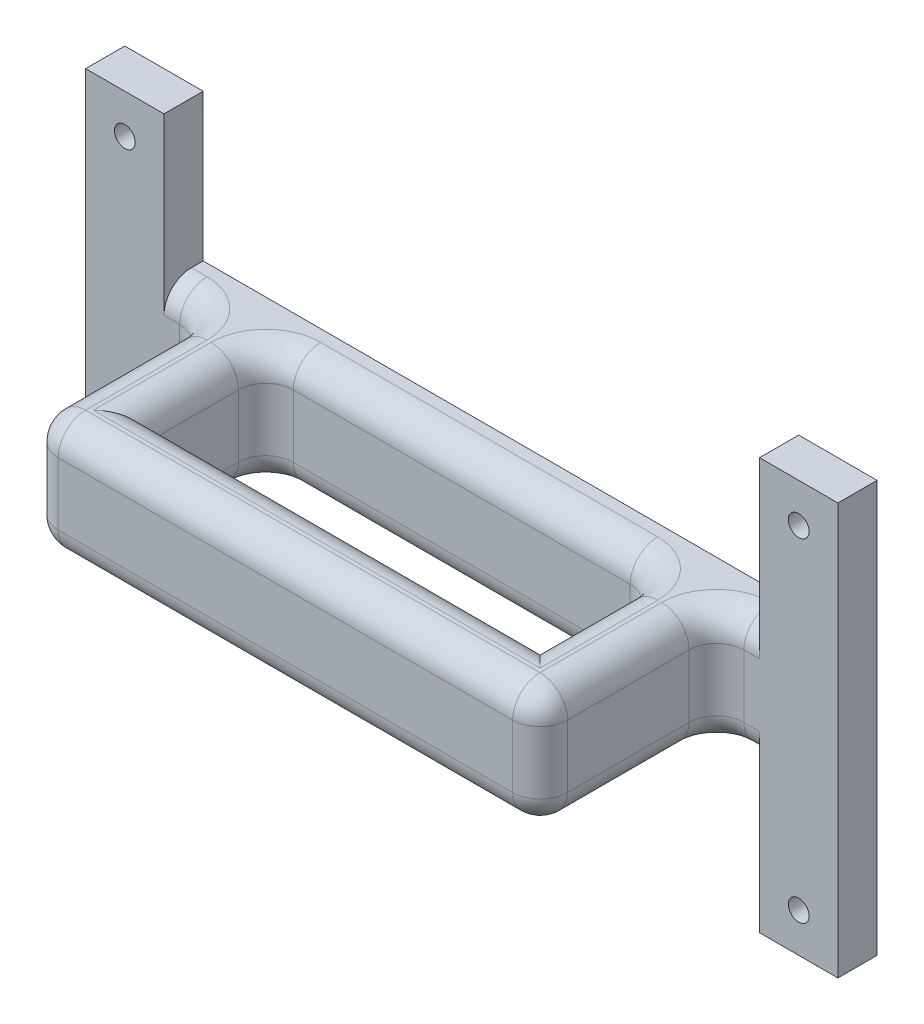
SolidWorks part; units mm, degrees
ref_plane "Front Plane" through (0, 0, 0) normal (0, 0, 1) x (1, 0, 0)
ref_plane "Top Plane" through (0, 0, 0) normal (0, 1, 0) x (1, 0, 0)
ref_plane "Right Plane" through (0, 0, 0) normal (1, 0, 0) x (0, 0, -1)
sketch "Sketch1" plane through (0, 0, 0) normal (0, 0, 1) x (1, 0, 0)
  line L1 (-96, 15) -> (96, 15)
  line L2 (-96, 15) -> (-96, -15)
  line L3 (-96, -15) -> (96, -15)
  line L4 (96, 15) -> (96, -15)
  line L5 (-96, 15) -> (96, -15) construction
  line L6 (-96, -15) -> (96, 15) construction
  line L7 (-96, 15) -> (-76, 15)
  line L8 (-96, 15) -> (-96, 52.5)
  line L9 (-96, 52.5) -> (-76, 52.5)
  line L10 (-76, 15) -> (-76, 52.5)
  line L11 (-96, -15) -> (-76, -15)
  line L12 (-96, -15) -> (-96, -52.5)
  line L13 (-96, -52.5) -> (-76, -52.5)
  line L14 (-76, -15) -> (-76, -52.5)
  line L15 (96, 15) -> (76, 15)
  line L16 (96, 15) -> (96, 52.5)
  line L17 (96, 52.5) -> (76, 52.5)
  line L18 (76, 15) -> (76, 52.5)
  line L19 (96, -15) -> (76, -15)
  line L20 (96, -15) -> (96, -52.5)
  line L21 (96, -52.5) -> (76, -52.5)
  line L22 (76, -15) -> (76, -52.5)
  point P0 (0, 0)
  dimension "D1" = 192
  dimension "D2" = 30
  dimension "D3" = 37.5
  dimension "D4" = 20
  dimension "D5" = 37.5
  dimension "D6" = 37.5
extrude "Boss-Extrude1" add sketch "Sketch1" along normal blind 10 contours L1 L10 L9 L8 | L4 L1 L2 L3 | L14 L3 L12 L13 | L3 L22 L21 L20 | L18 L1 L16 L17 region at (-86, 33.75, 0) region at (0, 0, 0) region at (-86, -33.75, 0) region at (86, 33.75, 0) region at (86, -33.75, 0)
hole_wizard "#4 (0.209) Diameter Hole1" positions "Sketch4" profile "Sketch5" hole size "#4" standard "ANSI Inch" end condition through all
sketch "Sketch4" plane through (0, 0, 10) normal (0, 0, 1) x (1, 0, 0)
  line L0 (-96, 52.5) -> (-76, 52.5) construction
  line L1 (-96, -52.5) -> (-96, 52.5) construction
  line L2 (76, 15) -> (76, 52.5) construction
  line L3 (96, 52.5) -> (76, 52.5) construction
  line L4 (-76, -15) -> (-76, -52.5) construction
  line L5 (-96, -52.5) -> (-76, -52.5) construction
  line L6 (76, -15) -> (76, -52.5) construction
  line L7 (96, -52.5) -> (76, -52.5) construction
  point P0 (-86, 42.5)
  point P2 (-86, -42.5)
  point P4 (86, -42.5)
  point P6 (86, 42.5)
  dimension "D1" = 10
  dimension "D2" = 10
  dimension "D3" = 10
  dimension "D4" = 10
  dimension "D5" = 10
  dimension "D6" = 10
  dimension "D7" = 10
  dimension "D8" = 10
sketch "Sketch5" plane through (-86, 42.5, 10) normal (1, 0, 0) x (0, -1, 0)
  line L0 (0, 0) -> (0, 10)
  line L1 (0, 10) -> (2.6543, 10)
  line L2 (2.6543, 10) -> (2.6543, 0)
  line L5 (2.6543, 0) -> (0, 0)
  line L11 (0, -6.35) -> (0, 107.95) construction
  dimension "Thru Hole Dia." = 5.3086
  dimension "Thru Hole Depth" = 10
sketch "Sketch6" plane through (0, 0, 10) normal (0, 0, 1) x (1, 0, 0)
  line L0 (-76, 15) -> (76, 15) construction
  line L1 (-50, 15) -> (50, 15)
  line L2 (-50, 15) -> (-50, -15)
  line L3 (-50, -15) -> (50, -15)
  line L4 (50, 15) -> (50, -15)
  line L5 (-76, -15) -> (76, -15) construction
  line L7 (-50, 15) -> (-65, 15)
  line L8 (-50, 15) -> (-50, -15)
  line L9 (-50, -15) -> (-65, -15)
  line L10 (-65, 15) -> (-65, -15)
  line L11 (50, 15) -> (65, 15)
  line L12 (50, 15) -> (50, -15)
  line L13 (50, -15) -> (65, -15)
  line L14 (65, 15) -> (65, -15)
  line M14 (-76, -15) -> (76, -15)
  line M20 (76, 15) -> (-76, 15)
  dimension "D1" = 50
  dimension "D2" = 50
  dimension "D3" = 15
  dimension "D4" = 15
extrude "Boss-Extrude2" add sketch "Sketch6" along normal blind 30 contours L10 L2 M20 M14 | L14 L4 M20 M14 region at (-57.5, 0, 10) region at (57.5, 0, 10)
extrude "Boss-Extrude3" add sketch "Sketch6<3>" along normal blind 15 from surface contours L4 L2 M20 M14 | L10 L2 M20 M14 | L14 L4 M20 M14 region at (0, 0, 10) region at (-57.5, 0, 10) region at (57.5, 0, 10) starting at face at (-57.5, 0, 40)
sketch "Sketch6<3>" plane through (0, 0, 10) normal (0, 0, 1) x (1, 0, 0) same geometry as "Sketch6"
fillet "Fillet2" radius 7 24 edges at (0, 15, 55) (0, -15, 55) (0, 15, 40) (0, -15, 40) (65, 0, 55) (-65, 0, 55) (50, -15, 25) (50, 15, 25) (-50, 15, 25) (-50, -15, 25) (-65, 0, 10) (65, 0, 10) (-70.5, -15, 10) (-70.5, 15, 10) (70.5, 15, 10) (70.5, -15, 10) (-65, -15, 32.5) (-65, 15, 32.5) (65, 15, 32.5) (65, -15, 32.5) (0, 15, 10) (0, -15, 10) (-50, 0, 10) (50, 0, 10)
